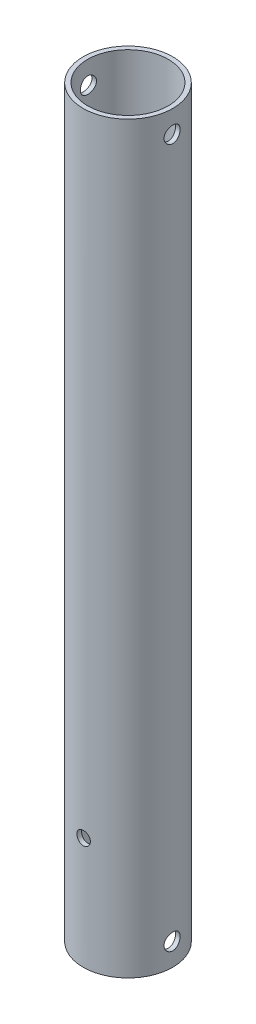
SolidWorks part; units mm, degrees
other "Boss-Extrude"
material "Toray T700"
ref_plane "Front" through (0, 0, 0) normal (0, 0, 1) x (1, 0, 0)
ref_plane "Top" through (0, 0, 0) normal (0, 1, 0) x (1, 0, 0)
ref_plane "Right" through (0, 0, 0) normal (1, 0, 0) x (0, 0, -1)
sketch "Sketch1" plane through (0, 0, 0) normal (0, 1, 0) x (1, 0, 0)
  line L5 (4.7969, 0) -> (-5.97, 0) construction
  circle A0 centre (0, 0) radius 10
  circle A1 centre (0, 0) radius 9
  dimension "D1" = 20
  dimension "D2" = 18
extrude "Boss-Extrude1" add sketch "Sketch1" along normal blind 166
ref_axis "Axis1" through (0, 0, 50) along (0, 0, -1)
ref_axis "Axis3" through (0, 166, 0) along (0, -1, 0)
ref_plane "Plane1" through (10, 0, 0) normal (1, 0, 0) x (0, 0, -1)
ref_plane "Plane2" through (0, 83, 0) normal (0, 1, 0) x (1, 0, 0)
hole_wizard "M3 Clearance Hole1" positions "Sketch5" profile "Sketch6" hole size "M3" standard "DIN" end condition through all
sketch "Sketch5" plane through (10, 0, 0) normal (1, 0, 0) x (0, 0, -1)
  line L0 (-10, 0) -> (10, 0) construction
  point P0 (0, 5)
  dimension "D1" = 5
sketch "Sketch6" plane through (10, 5, 0) normal (0, 1, 0) x (0, 0, -1)
  line L0 (0, 0) -> (0, 20)
  line L1 (0, 20) -> (1.8, 20)
  line L2 (1.8, 20) -> (1.8, 0)
  line L5 (1.8, 0) -> (0, 0)
  line L11 (0, -6.35) -> (0, 107.95) construction
  dimension "Thru Hole Dia." = 3.6
  dimension "Thru Hole Depth" = 20
mirror "Mirror1" about plane through (0, 83, 0) normal (0, 1, 0) of "M3 Clearance Hole1"
sketch "Sketch7" plane through (0, 0, 0) normal (0, 0, 1) x (1, 0, 0)
  line L0 (-10, 0) -> (10, 0) construction
  circle A0 centre (0, 25) radius 1.5
  dimension "D1" = 3
  dimension "D2" = 25
extrude "Cut-Extrude1" cut sketch "Sketch7" along normal up to next
sketch "Sketch8" plane through (0, 0, 0) normal (0, 0, 1) x (1, 0, 0)
  line L0 (10, 166) -> (-10, 166) construction
  line L1 (0, 141) -> (0, 166) construction
  circle A0 centre (0, 141) radius 1.5
  dimension "D1" = 3
  dimension "D2" = 25
extrude "Cut-Extrude2" cut sketch "Sketch8" against normal through all
